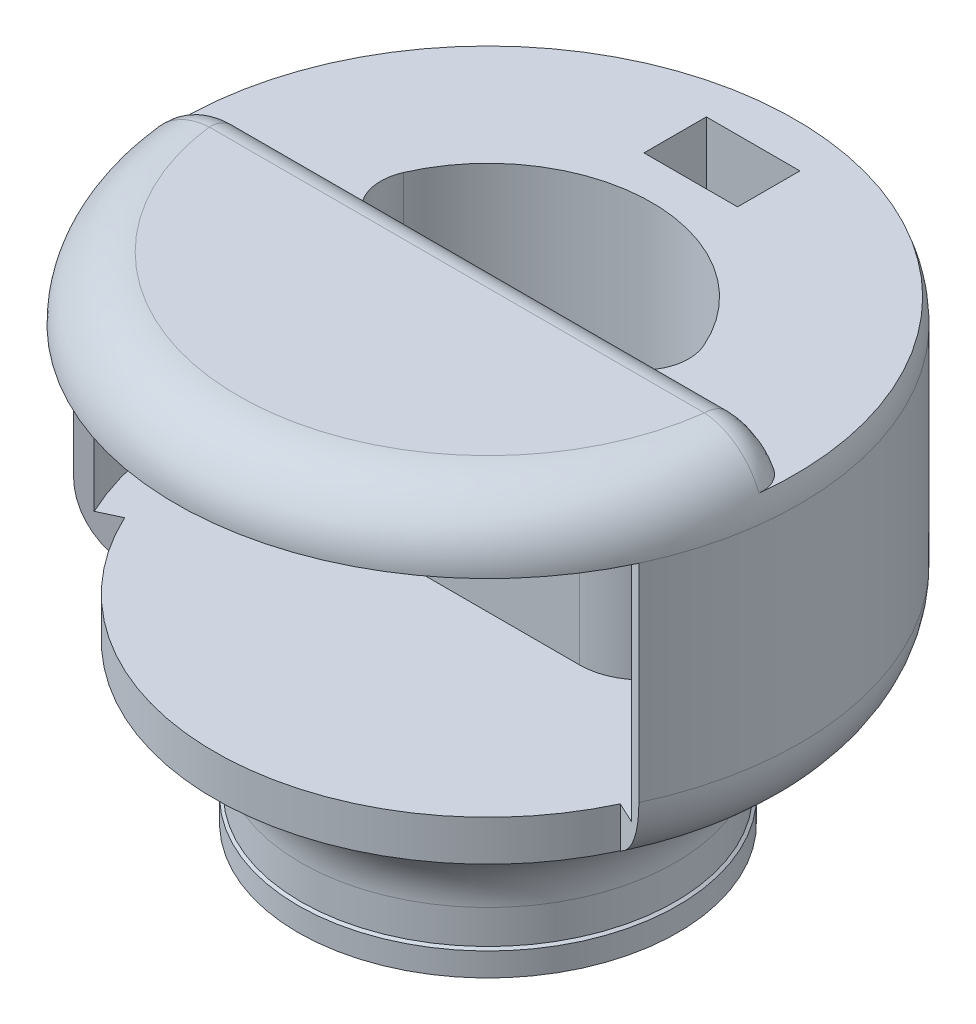
SolidWorks part; units mm, degrees
ref_plane "Front Plane" through (0, 0, 0) normal (0, 0, 1) x (1, 0, 0)
ref_plane "Top Plane" through (0, 0, 0) normal (0, 1, 0) x (1, 0, 0)
ref_plane "Right Plane" through (0, 0, 0) normal (1, 0, 0) x (0, 0, -1)
sketch "Sketch1" plane through (0, 0, 0) normal (0, 0, 1) x (1, 0, 0)
  line L0 (0, 0) -> (0, 90.2242) construction
  line L28 (0, 63.4279) -> (32, 63.4279)
  line L29 (40, 55.4279) -> (40, 28.8468)
  line L30 (22.5, 0) -> (24.35, 0)
  line L31 (24.35, 0) -> (24.35, 3)
  line L32 (24.35, 3) -> (24, 3.25)
  line L33 (24, 3.25) -> (24, 7.5811)
  line L34 (28.5399, 15.9588) -> (35.4601, 20.4691)
  line L35 (0, 13) -> (22, 13)
  line L36 (22.5, 12.5) -> (22.5, 0)
  line L37 (0, 13) -> (0, 63.4279)
  arc A0 (22, 13) -> (22.5, 12.5) centre (22, 12.5) cw
  arc A1 (24, 7.5811) -> (28.5399, 15.9588) centre (34, 7.5811) cw
  arc A2 (35.4601, 20.4691) -> (40, 28.8468) centre (30, 28.8468) ccw
  arc A3 (32, 63.4279) -> (40, 55.4279) centre (32, 55.4279) cw
  point P11 (22.9, 63.4279)
  point P18 (22.5, 13)
  point P21 (24, 13)
  point P24 (40, 23.4279)
  point P27 (40, 63.4279)
  point P28 (28.5604, 23.4279)
  point P31 (22.5, 17)
  dimension "D8" = 9.75
  dimension "D9" = 0.5
  dimension "D4" = 1.85
  dimension "D1" = 22.5
  dimension "D10" = 10
  dimension "D11" = 10
  dimension "D12" = 8
  dimension "D2" = 40
  dimension "D3" = 40
  dimension "D5" = 1.5
  dimension "D6" = 3
  dimension "D7" = 13
revolve "Revolve1" add sketch "Sketch1" angle 360 about L0
ref_plane "Plane1" through (0, 13, 0) normal (0, -1, 0) x (-1, 0, 0)
sketch "Sketch18" plane through (0, 0, 0) normal (0, 0, 1) x (1, 0, 0)
  line L0 (0, 0) -> (0, 101.5813) construction
  line L1 (-24.35, 0) -> (24.35, 0) construction
sketch "Sketch3" plane through (0, 0, 0) normal (0, 0, 1) x (1, 0, 0)
  point P0 (1.2404, 19.1989)
ref_point "Point1"
ref_plane "Plane2" through (0, 0, 22.9) normal (0, 0, 1) x (1, 0, 0)
ref_plane "Plane3" through (0, 0, 40) normal (0, 0, 1) x (1, 0, 0)
ref_plane "Plane4" through (0, 55.4279, 0) normal (0, 1, 0) x (1, 0, 0)
sketch "Sketch9" plane through (0, 55.4279, 0) normal (0, 1, 0) x (1, 0, 0)
  circle A7 centre (0, 0) radius 38
  circle A8 centre (0, 0) radius 40 construction
  circle A9 centre (0, 0) radius 23
  dimension "D1" = 2
  dimension "D2" = 46
ref_plane "Plane5" through (0, 13, 0) normal (0, -1, 0) x (-1, 0, 0)
sketch "Sketch11" plane through (0, 13, 0) normal (0, -1, 0) x (-1, 0, 0)
  line L0 (-21, 0) -> (21, 0)
  arc A1 (-21, 0) -> (21, 0) centre (0, 0) cw
  dimension "D1" = 42
extrude "Cut-Extrude3" cut sketch "Sketch11" against normal blind 60
ref_plane "Plane6" through (0, 0, -40) normal (0, 0, -1) x (-1, 0, 0)
extrude "Cut-Extrude5" cut sketch "Sketch9" against normal blind 30 and the other way blind 2
sketch "Sketch19" plane through (0, 0, 0) normal (1, 0, 0) x (0, 0, -1)
  line L0 (-47.0647, 55.4279) -> (-35.0647, 55.4279)
  line L1 (31.2976, 55.4279) -> (-31.2976, 55.4279) construction
  line L2 (-35.0647, 55.4279) -> (-35.0647, 18.9279)
  line L3 (-35.0647, 18.9279) -> (-47.0647, 18.9279)
  line L4 (-47.0647, 18.9279) -> (-47.0647, 55.4279)
  dimension "D1" = 12
  dimension "D2" = 36.5
revolve "Cut-Revolve2" cut sketch "Sketch19" angle 65 about L0 other way angle 65
ref_plane "Plane7" through (0, 0, 22.5) normal (0, 0, -1) x (-1, 0, 0)
sketch "Sketch21" plane through (0, 0, 22.5) normal (0, 0, -1) x (-1, 0, 0)
  line L0 (0, 0) -> (0, 101.5813) construction
  line L1 (-1.625, 4) -> (1.625, 4)
  line L2 (-1.625, 4) -> (-1.625, 0)
  line L3 (-1.625, 0) -> (1.625, 0)
  line L4 (1.625, 4) -> (1.625, 0)
  line L5 (-1.625, 4) -> (1.625, 0) construction
  line L6 (-1.625, 0) -> (1.625, 4) construction
  line L7 (-22.5, 0) -> (22.5, 0) construction
  point P0 (0, 2)
  dimension "D1" = 4
  dimension "D2" = 3.25
extrude "Boss-Extrude3" add sketch "Sketch21" along normal blind 1.35
pattern_circular "CirPattern1" count 5 over 360 about axis through (0, 0, 0) along (0, -1, 0) of "Boss-Extrude3"
ref_plane "Plane8" through (0, 20.4691, 0) normal (0, 1, 0) x (1, 0, 0)
sketch "Sketch22" plane through (0, 63.4279, 0) normal (0, 1, 0) x (1, 0, 0)
  line L0 (-40, 0) -> (40, 0)
  arc A0 (-40, 0) -> (40, 0) centre (0, 0) cw
  arc A1 (36.2523, -16.9047) -> (-36.2523, -16.9047) centre (0, 0) ccw construction
extrude "Cut-Extrude9" cut sketch "Sketch22" against normal blind 5
sketch "Sketch23" plane through (0, 0, -40) normal (0, 0, -1) x (-1, 0, 0)
  line L0 (0, 0) -> (0, 101.5813) construction
  line L1 (31.2976, 55.4279) -> (-31.2976, 55.4279) construction
  circle A0 centre (0, 42.1379) radius 10.5
  dimension "D1" = 21
  dimension "D2" = 13.29
extrude "Cut-Extrude10" cut sketch "Sketch23" against normal blind 10
sketch "Sketch24" plane through (0, 58.4279, 0) normal (0, 1, 0) x (1, 0, 0)
  line L1 (-8.5, 36) -> (8.5, 36)
  line L2 (-8.5, 36) -> (-8.5, 24)
  line L3 (-8.5, 24) -> (8.5, 24)
  line L4 (8.5, 36) -> (8.5, 24)
  line L5 (-8.5, 36) -> (8.5, 24) construction
  line L6 (-8.5, 24) -> (8.5, 36) construction
  arc A0 (39.4162, 0) -> (-39.4162, 0) centre (0, 0) ccw construction
  point P0 (0, 30)
  dimension "D1" = 30
  dimension "D2" = 12
  dimension "D3" = 17
extrude "Boss-Extrude4" add sketch "Sketch24" against normal blind 8
sketch "Sketch26" plane through (0, 58.4279, 0) normal (0, 1, 0) x (1, 0, 0)
  line L1 (-6, 34) -> (6, 34)
  line L2 (-6, 34) -> (-6, 26)
  line L3 (-6, 26) -> (6, 26)
  line L4 (6, 34) -> (6, 26)
  line L5 (-6, 34) -> (6, 26) construction
  line L6 (-6, 26) -> (6, 34) construction
  arc A0 (39.4162, 0) -> (-39.4162, 0) centre (0, 0) ccw construction
  point P0 (0, 30)
  dimension "D1" = 30
  dimension "D2" = 8
  dimension "D3" = 12
extrude "Cut-Extrude11" cut sketch "Sketch26" against normal blind 10
sketch "Sketch27" plane through (8.5, 0, 0) normal (1, 0, 0) x (0, 0, -1)
  line L0 (36, 50.4279) -> (36, 57.4279) construction
  line L1 (27.5, 56.4279) -> (31.5, 56.4279)
  line L2 (27.5, 56.4279) -> (27.5, 51.4279)
  line L3 (27.5, 51.4279) -> (31.5, 51.4279)
  line L4 (31.5, 56.4279) -> (31.5, 51.4279)
  line L5 (27.5, 56.4279) -> (31.5, 51.4279) construction
  line L6 (27.5, 51.4279) -> (31.5, 56.4279) construction
  line L7 (24, 50.4279) -> (24, 57.4279) construction
  line L8 (24, 50.4279) -> (36, 50.4279) construction
  point P0 (29.5, 53.9279)
  dimension "D1" = 12
  dimension "D2" = 3.5
  dimension "D3" = 5
  dimension "D4" = 4
  dimension "D5" = 5.5
extrude "Cut-Extrude12" cut sketch "Sketch27" against normal blind 5
ref_plane "Plane9" through (-39.4162, 58.4279, 0) normal (0.375, 0.927, 0) x (0.927, -0.375, 0)
ref_plane "Plane10" through (0, 58.4279, 0) normal (0, 1, 0) x (1, 0, 0)
sketch "Sketch28" plane through (0, 55.4279, 0) normal (0, 1, 0) x (1, 0, 0)
  line L0 (-22.9129, -2) -> (22.9129, -2)
  arc A0 (-22.9129, -2) -> (22.9129, -2) centre (0, 0) ccw
  dimension "D1" = 46
  dimension "D2" = 2
extrude "Cut-Extrude14" cut sketch "Sketch28" against normal blind 30 and the other way blind 2
sketch "Sketch29" plane through (0, 0, 0) normal (0, 0, -1) x (-1, 0, 0)
  line L0 (0, 0) -> (0, 101.5813) construction
  line L1 (32, 63.4279) -> (-32, 63.4279) construction
  circle A0 centre (-30.4162, 60.9279) radius 1
  circle A1 centre (30.4162, 60.9279) radius 1
  circle A2 centre (0, 60.9279) radius 1
  dimension "D1" = 2
  dimension "D2" = 2
  dimension "D3" = 2
  dimension "D4" = 2.5
  dimension "D5" = 2.5
  dimension "D6" = 2.5
  dimension "D7" = 9
  dimension "D8" = 9
extrude "Cut-Extrude15" cut sketch "Sketch29" against normal blind 15
fillet "Fillet1" radius 6 2 edges at (-21, 35.7139, 0) (21, 35.7139, 0)
fillet "Fillet2" radius 8 2 edges at (22.9129, 41.4279, 2) (-22.9129, 41.4279, 2)
fillet "Fillet3" radius 4 3 edges at (-36.4721, 62.0611, 0) (36.4721, 62.0611, 0) (0, 63.4279, 0)
